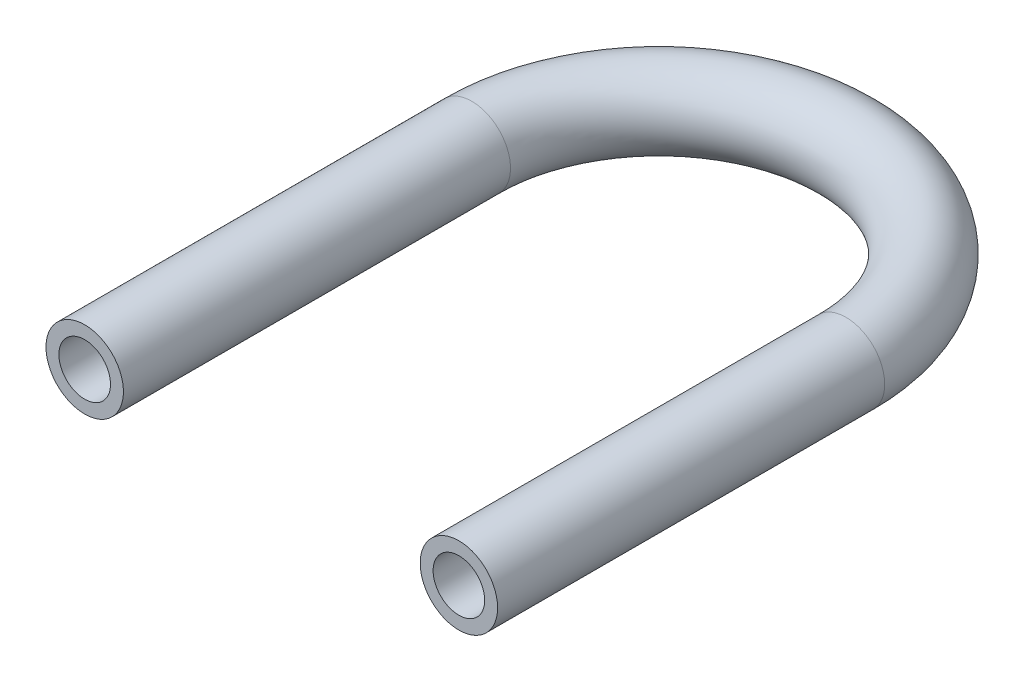
SolidWorks part; units mm, degrees
ref_plane "Front Plane" through (0, 0, 0) normal (0, 0, 1) x (1, 0, 0)
ref_plane "Top Plane" through (0, 0, 0) normal (0, 1, 0) x (1, 0, 0)
ref_plane "Right Plane" through (0, 0, 0) normal (1, 0, 0) x (0, 0, -1)
sketch "Sketch1" plane through (0, 0, 0) normal (0, 1, 0) x (1, 0, 0)
  line L0 (-14.5, 0) -> (-14.5, -30)
  line L1 (14.5, 0) -> (14.5, -30)
  arc A0 (-14.5, 0) -> (14.5, 0) centre (0, 0) cw
  point P6 (0, 0)
  dimension "D1" = 14.5
  dimension "D2" = 30
ref_plane "Plane1" through (-14.5, 0, 30) normal (0, 0, -1) x (-1, 0, 0)
sketch "Sketch2" plane through (-14.5, 0, 30) normal (0, 0, -1) x (-1, 0, 0)
  circle A0 centre (0, 0) radius 3
  circle A1 centre (0, 0) radius 2
  dimension "D1" = 6
  dimension "D2" = 4
sweep "Sweep1" add profiles "Sketch2" path "Sketch1"
